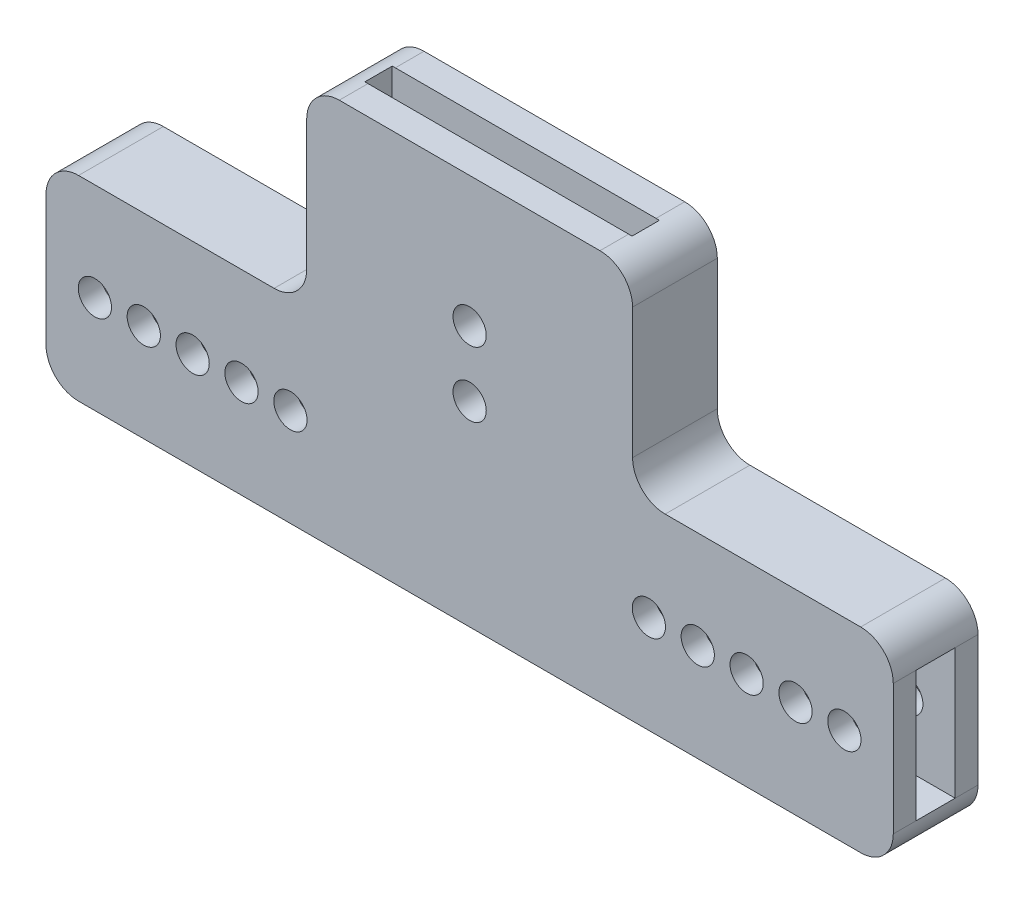
SolidWorks part; units mm, degrees
ref_plane "Front Plane" through (0, 0, 0) normal (0, 0, 1) x (1, 0, 0)
ref_plane "Top Plane" through (0, 0, 0) normal (0, 1, 0) x (1, 0, 0)
ref_plane "Right Plane" through (0, 0, 0) normal (1, 0, 0) x (0, 0, -1)
sketch "Sketch1" plane through (0, 0, 0) normal (0, 0, 1) x (1, 0, 0)
  line L1 (-25, 30) -> (25, 30)
  line L2 (-25, 30) -> (-25, -30)
  line L3 (-25, -30) -> (25, -30)
  line L4 (25, 30) -> (25, -30)
  line L5 (-25, 30) -> (25, -30) construction
  line L6 (-25, -30) -> (25, 30) construction
  point P0 (0, 0)
extrude "Boss-Extrude1" add sketch "Sketch1" along normal blind 13
sketch "Sketch2" plane through (0, 30, 0) normal (0, 1, 0) x (1, 0, 0)
  line L0 (0, 0) -> (0, -13) construction
  line L1 (-20.5, -4.4) -> (20.5, -4.4)
  line L2 (-20.5, -4.4) -> (-20.5, -8.6)
  line L3 (-20.5, -8.6) -> (20.5, -8.6)
  line L4 (20.5, -4.4) -> (20.5, -8.6)
  line L5 (-20.5, -4.4) -> (20.5, -8.6) construction
  line L6 (-20.5, -8.6) -> (20.5, -4.4) construction
  line L7 (25, 0) -> (-25, 0) construction
  line L8 (-25, -6.5) -> (25, -6.5) construction
  line L9 (-25, -13) -> (-25, 0) construction
  line L10 (25, -13) -> (25, 0) construction
  line L11 (25, -13) -> (-25, -13) construction
  point P0 (0, -6.5)
  point P17 (0, 0)
  point P18 (0, 0)
  dimension "D2" = 4.2
  dimension "D3" = 41
extrude "Cut-Extrude1" cut sketch "Sketch2" against normal through all
sketch "Sketch3" plane through (-25, 0, 0) normal (-1, 0, 0) x (0, 0, 1)
  line L0 (13, 30) -> (13, -30) construction
  line L1 (0, -30) -> (13, -30)
  line L2 (0, -30) -> (0, 0)
  line L3 (0, 0) -> (13, 0)
  line L4 (13, -30) -> (13, 0)
  line L5 (6.5, 0) -> (6.5, -30) construction
  line L6 (0, -15) -> (13, -15) construction
  point P1024 (6.5, -15)
  dimension "D1" = 30
extrude "Boss-Extrude2" add sketch "Sketch3" along normal blind 40
sketch "Sketch4" plane through (-65, 0, 0) normal (-1, 0, 0) x (0, 0, 1)
  line L0 (13, 0) -> (0, 0) construction
  line L1 (3.5, -5) -> (9.5, -5)
  line L2 (3.5, -5) -> (3.5, -25)
  line L3 (3.5, -25) -> (9.5, -25)
  line L4 (9.5, -5) -> (9.5, -25)
  line L5 (3.5, -5) -> (9.5, -25) construction
  line L6 (3.5, -25) -> (9.5, -5) construction
  line L9 (0, -30) -> (13, -30) construction
  line L10 (6.5, 0) -> (6.5, -30) construction
  point P0 (6.5, -15)
  dimension "D1" = 5
  dimension "D2" = 3
  dimension "D3" = 3
  dimension "D4" = 5
extrude "Cut-Extrude2" cut sketch "Sketch4" against normal blind 40
sketch "Sketch5" plane through (0, 0, 13) normal (0, 0, 1) x (1, 0, 0)
  line L0 (-65, -5) -> (-65, -25) construction
  circle A0 centre (-57.5, -14.9958) radius 2.55
  circle A1 centre (-50, -14.9958) radius 2.55
  circle A2 centre (-42.5, -14.9958) radius 2.55
  circle A3 centre (-35, -14.9958) radius 2.55
  circle A4 centre (-27.5, -14.9958) radius 2.55
  dimension "D1" = 5
  dimension "D3" = 5.1
  dimension "D2" = 7.5
extrude "Cut-Extrude3" cut sketch "Sketch5" against normal blind 35
mirror "Mirror1" about plane through (0, 0, 0) normal (1, 0, 0) of "Cut-Extrude3", "Cut-Extrude2", "Boss-Extrude2"
fillet "Fillet1" radius 5 8 edges at (65, -30, 6.5) (65, 0, 6.5) (25, 0, 6.5) (-65, -30, 6.5) (-65, 0, 6.5) (-25, 0, 6.5) (25, 30, 6.5) (-25, 30, 6.5)
sketch "Sketch6" plane through (0, 0, 13) normal (0, 0, 1) x (1, 0, 0)
  circle A0 centre (0, 0) radius 2.55
  circle A1 centre (0, 10) radius 2.55
  dimension "D1" = 10
extrude "Cut-Extrude4" cut sketch "Sketch6" against normal blind 35
